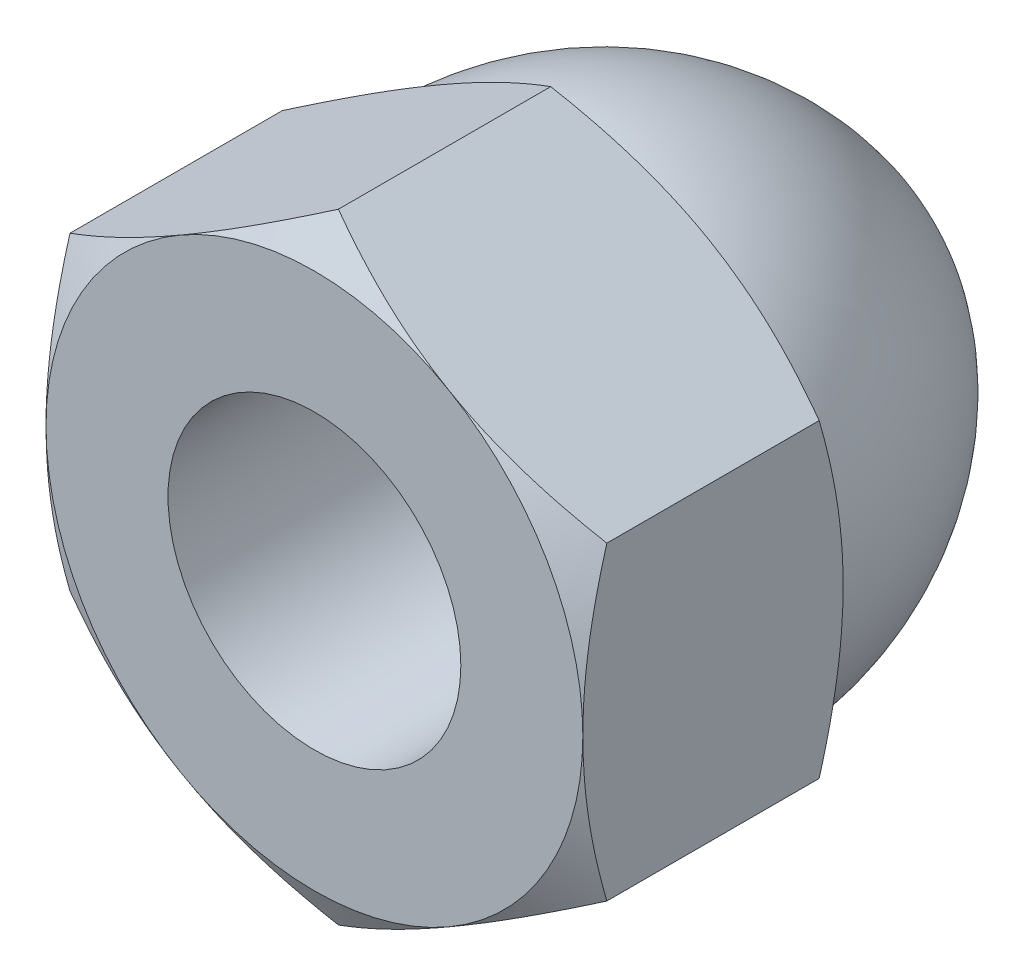
SolidWorks part; units mm, degrees
ref_plane "Front Plane" through (0, 0, 0) normal (0, 0, 1) x (1, 0, 0)
ref_plane "Top Plane" through (0, 0, 0) normal (0, 1, 0) x (1, 0, 0)
ref_plane "Right Plane" through (0, 0, 0) normal (1, 0, 0) x (0, 0, -1)
sketch "Sketch1" plane through (0, 0, 0) normal (0, 0, 1) x (1, 0, 0)
  line L1 (0, 3.1754) -> (-2.75, 1.5877)
  line L2 (-2.75, 1.5877) -> (-2.75, -1.5877)
  line L3 (-2.75, -1.5877) -> (0, -3.1754)
  line L4 (0, -3.1754) -> (2.75, -1.5877)
  line L5 (2.75, -1.5877) -> (2.75, 1.5877)
  line L6 (2.75, 1.5877) -> (0, 3.1754)
  circle A0 centre (0, 0) radius 2.75 construction
extrude "Extrude1" add sketch "Sketch1" against normal blind 2.6667
sketch "Sketch2" plane through (0, 0, 0) normal (0, 0, 1) x (1, 0, 0)
  circle A0 centre (0, 0) radius 2.75 construction
  circle A1 centre (0, 0) radius 2.75
extrude "Cut-Extrude1" cut sketch "Sketch2" against normal through all draft 60 flip side to cut
sketch "Sketch3" plane through (0, 0, -2.6667) normal (0, 0, -1) x (-1, 0, 0)
  circle A1 centre (0, 0) radius 2.75
  circle A2 centre (0, 0) radius 2.75
  dimension "D1" = 0
extrude "Cut-Extrude2" cut sketch "Sketch3" against normal through all draft 60 flip side to cut
sketch "Sketch14" plane through (0, 0, 0) normal (1, 0, 0) x (0, 0, -1)
  line L0 (2.6667, 2.7225) -> (2.6667, 0)
  line L1 (2.6667, 0) -> (6, 0)
  line L2 (2.6667, 0) -> (2.6667, 2.3816) construction
  line L3 (2.6667, 2.75) -> (11.6149, 2.75) construction
  line L4 (2.6667, 2.7225) -> (14.0961, 2.7225) construction
  line L6 (0, 0) -> (2.6667, 0) construction
  arc A0 (2.6667, 2.7225) -> (6, 0) centre (2.6667, -0.6794) cw
  dimension "overall length" = 6
  dimension "D1" = 5.445
revolve "Revolve1" add sketch "Sketch14" angle 360 about L6
sketch "Sketch4" plane through (0, 0, 0) normal (0, 0, 1) x (1, 0, 0)
  circle A0 centre (0, 0) radius 1.5
  dimension "Thread Dia" = 3
extrude "Cut-Extrude3" cut sketch "Sketch4" against normal blind 5
sketch "Sketch5" plane through (0, 0, 0) normal (0, 0, 1) x (1, 0, 0)
  circle A0 centre (0, 0) radius 1.5 construction
  circle A1 centre (0, 0) radius 1.5
sketch "Sketch15" plane through (0, 0, -5) normal (0, 0, 1) x (1, 0, 0)
  circle A0 centre (0, 0) radius 1.5 construction
  circle A1 centre (0, 0) radius 1.5
curve "Helix/Spiral2" pitch 0.5 height 7 turns 14 parameters "pitch"=0.5
sketch "Sketch18" plane through (0, 0, 0) normal (0, 0, 1) x (1, 0, 0)
  circle A0 centre (0, 0) radius 1.5 construction
  circle A1 centre (0, 0) radius 1.5
sketch "Sketch16" plane through (0, 0, 0) normal (1, 0, 0) x (0, 0, -1)
  line L0 (5, 1.5) -> (5.4375, 1.5)
  line L1 (5.4375, 1.5) -> (5.25, 1.1752)
  line L2 (5.25, 1.1752) -> (5.1875, 1.1752)
  line L3 (5.1875, 1.1752) -> (5, 1.5)
  line L4 (5.2188, 1.1752) -> (5.2188, 1.5) construction
  line L5 (5.0938, 1.3376) -> (5.3438, 1.3376) construction
  line L6 (5, 1.5) -> (5, -1.5) construction
  dimension "D1" = 60
  dimension "D2" = 0.0625
  dimension "D3" = 0.25
sweep "Sweep1" [suppressed] add profiles "Sketch16" path "Helix/Spiral2"
sketch "Sketch17" plane through (0, 0, 0) normal (0, 0, 1) x (1, 0, 0)
  line L6 (0, 3.1754) -> (-2.75, 1.5877)
  line L7 (-2.75, 1.5877) -> (-2.75, -1.5877)
  line L8 (-2.75, -1.5877) -> (0, -3.1754)
  line L9 (0, -3.1754) -> (2.75, -1.5877)
  line L10 (2.75, -1.5877) -> (2.75, 1.5877)
  line L11 (2.75, 1.5877) -> (0, 3.1754)
  line L12 (0, 3.1754) -> (-2.75, 1.5877)
  line L13 (-2.75, 1.5877) -> (-2.75, -1.5877)
  line L14 (-2.75, -1.5877) -> (0, -3.1754)
  line L15 (0, -3.1754) -> (2.75, -1.5877)
  line L16 (2.75, -1.5877) -> (2.75, 1.5877)
  line L17 (2.75, 1.5877) -> (0, 3.1754)
  dimension "D1" = 0
extrude "Cut-Extrude8" [suppressed] cut sketch "Sketch17" along normal through all
extrude "Cut-Extrude9" [suppressed] cut sketch "Sketch18" against normal through all draft 45
sketch "Sketch20" plane through (0, 0, 0) normal (1, 0, 0) x (0, 0, -1)
  line L0 (5.1667, 1.5) -> (6.0327, 0)
  line L1 (5, 1.5) -> (5.1667, 1.5)
  line L2 (5, 1.5) -> (5, 0)
  line L3 (5, 1.5) -> (5.4375, 1.5) construction
  line L4 (5, 1.5) -> (5, -1.5) construction
  line L5 (5, 0) -> (6.0327, 0)
  line L6 (0, 0) -> (-3.6507, 0) construction
  dimension "D1" = 0.1667
  dimension "D2" = 60
revolve "Cut-Revolve1" cut sketch "Sketch20" angle 360 about L6
equation "\"D2@Sketch16\" = \"pitch@Helix/Spiral2\"*.125"
equation "\"D3@Sketch16\" = \"pitch@Helix/Spiral2\"*.50"
equation "\"D1@Sketch20\" = \"pitch@Helix/Spiral2\"/3"
equation "\"D3@Helix/Spiral2\" = \"Thread Depth@Cut-Extrude3\"+2"
equation "\"Nut Height@Extrude1\" = \"overall length@Sketch14\"/2.25"
equation "\"D1@Sketch14\" = \"Hex@Sketch1\"*.99"
